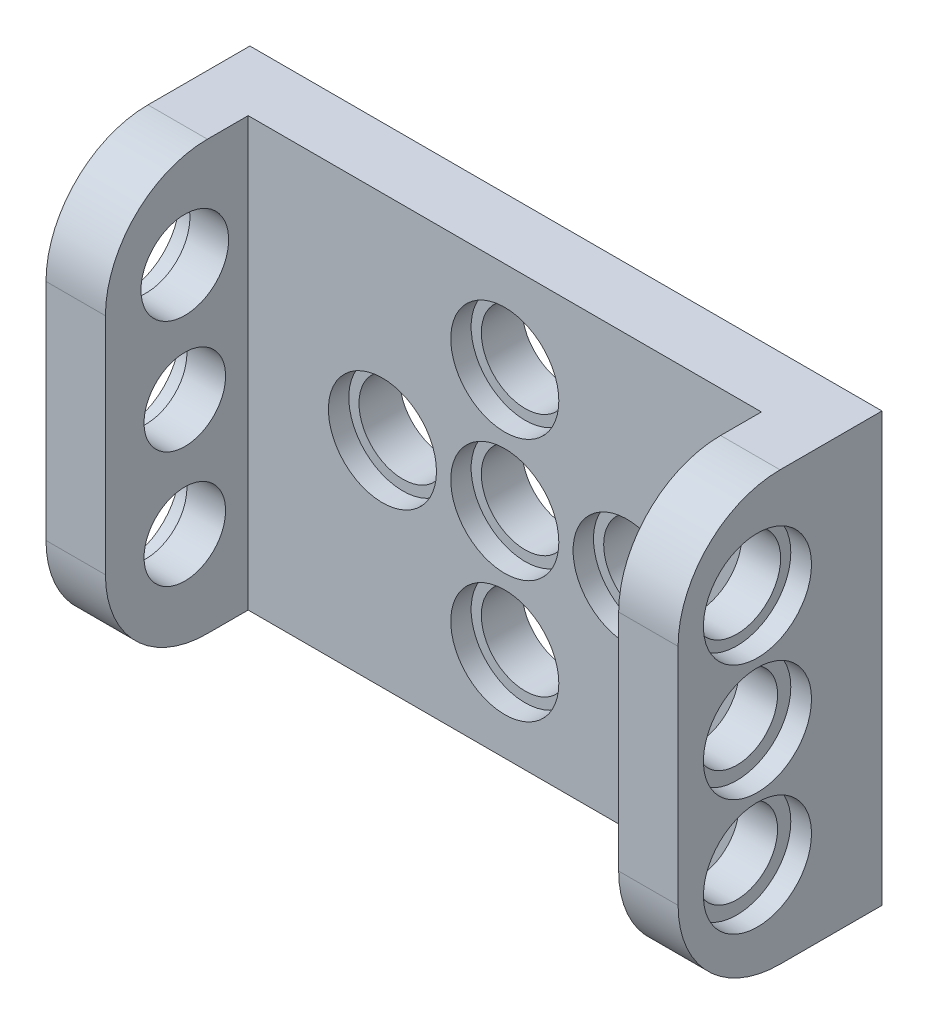
SolidWorks part; units mm, degrees
ref_plane "Alzado" through (0, 0, 0) normal (0, 0, 1) x (1, 0, 0)
ref_plane "Planta" through (0, 0, 0) normal (0, 1, 0) x (1, 0, 0)
ref_plane "Vista lateral" through (0, 0, 0) normal (1, 0, 0) x (0, 0, -1)
sketch "Croquis1" plane through (0, 0, 0) normal (0, 0, 1) x (1, 0, 0)
  line L1 (13.077, 21.3579) -> (44.077, 21.3579)
  line L2 (13.077, 21.3579) -> (13.077, 0.3579)
  line L3 (13.077, 0.3579) -> (44.077, 0.3579)
  line L4 (44.077, 21.3579) -> (44.077, 0.3579)
  dimension "D1" = 21
  dimension "D2" = 31
extrude "Saliente-Extruir1" add sketch "Croquis1" along normal blind 10
sketch "Croquis2" plane through (0, 0, 10) normal (0, 0, 1) x (1, 0, 0)
  line L0 (28.577, 21.3579) -> (28.577, 0.3579) construction
  line L1 (44.077, 21.3579) -> (13.077, 21.3579) construction
  line L2 (13.077, 0.3579) -> (44.077, 0.3579) construction
  line L3 (28.577, 10.8579) -> (44.077, 10.8579) construction
  line L4 (44.077, 0.3579) -> (44.077, 21.3579) construction
  line L6 (15.992, 21.3579) -> (41.162, 21.3579)
  line L7 (15.992, 21.3579) -> (15.992, 0.3579)
  line L8 (15.992, 0.3579) -> (41.162, 0.3579)
  line L9 (41.162, 21.3579) -> (41.162, 0.3579)
  line L10 (15.992, 21.3579) -> (41.162, 0.3579) construction
  line L11 (15.992, 0.3579) -> (41.162, 21.3579) construction
  dimension "D1" = 25.17
extrude "Cortar-Extruir1" cut sketch "Croquis2" against normal blind 7
sketch "Croquis3" plane through (0, 0, 0) normal (0, 0, -1) x (-1, 0, 0)
  line L0 (-28.577, 21.3579) -> (-28.577, 0.3579) construction
  line L1 (-44.077, 21.3579) -> (-13.077, 21.3579) construction
  line L2 (-13.077, 0.3579) -> (-44.077, 0.3579) construction
  line L3 (-28.577, 10.8579) -> (-13.077, 10.8579) construction
  line L4 (-13.077, 21.3579) -> (-13.077, 0.3579) construction
sketch "Croquis4" plane through (0, 0, 0) normal (0, 0, 1) x (1, 0, 0)
  line L0 (28.577, 16.8579) -> (28.577, 10.8579) construction
  line L1 (28.577, 10.8579) -> (28.577, 4.8579) construction
  line L16 (34.577, 10.8579) -> (22.577, 10.8579) construction
  line L18 (22.577, 10.8579) -> (28.577, 16.8579) construction
  line L19 (28.577, 16.8579) -> (34.577, 10.8579) construction
  line L20 (28.577, 4.8579) -> (22.577, 10.8579) construction
  line L21 (34.577, 10.8579) -> (28.577, 4.8579) construction
sketch "Croquis5" plane through (0, 0, 0) normal (0, 0, -1) x (-1, 0, 0)
  circle A0 centre (-28.577, 16.8579) radius 2.15
  circle A1 centre (-22.577, 10.8579) radius 2.15
  circle A2 centre (-34.577, 10.8579) radius 2.15
  circle A3 centre (-28.577, 4.8579) radius 2.15
  circle A4 centre (-28.577, 16.8579) radius 2.65
  circle A5 centre (-22.577, 10.8579) radius 2.65
  circle A6 centre (-34.577, 10.8579) radius 2.65
  circle A7 centre (-28.577, 4.8579) radius 2.65
  circle A8 centre (-28.577, 10.8579) radius 2.15
  circle A9 centre (-28.577, 10.8579) radius 2.65
  dimension "D1" = 5.3
  dimension "D2" = 4.3
extrude "Cortar-Extruir2" cut sketch "Croquis5" against normal through all contours A0 | A8 | A1 | A2 | A3 region at (28.577, 16.8579, 0) region at (22.577, 10.8579, 0) region at (34.577, 10.8579, 0) region at (28.577, 4.8579, 0) region at (28.577, 10.8579, 0)
sketch "Croquis6" plane through (44.077, 0, 0) normal (1, 0, 0) x (0, 0, -1)
  line L0 (-3.0446, 21.3579) -> (-3.0446, 0.3579) construction
  line L1 (-10, 21.3579) -> (0, 21.3579) construction
  line L2 (-10, 0.3579) -> (0, 0.3579) construction
  line L3 (-3.0446, 10.8579) -> (0, 10.8579) construction
  line L4 (0, 21.3579) -> (0, 0.3579) construction
  line L5 (-8.965, 10.8579) -> (-3.2501, 10.8579) construction
  line L6 (-3.2501, 10.8579) -> (2.4649, 10.8579) construction
  line L7 (2.4649, 10.8579) -> (6.3749, 10.8579) construction
  line L8 (-8.965, 10.8579) -> (-12.8751, 10.8579) construction
  line L9 (-8.965, 8.3579) -> (-8.965, 7.8579) construction
  line L10 (-3.2501, 8.3579) -> (-3.2501, 7.8579) construction
  line L11 (2.4649, 8.3579) -> (2.4649, 7.8579) construction
  line L12 (-6.1076, 21.3579) -> (-6.1076, 10.8579) construction
  line L13 (-6.1076, 10.8579) -> (-6.1076, 0.3579) construction
  circle A0 centre (-6.1076, 5.143) radius 2.65
  circle A1 centre (-6.1076, 10.8579) radius 2.65
  circle A2 centre (-6.1076, 16.5729) radius 2.65
  circle A3 centre (-6.1076, 5.143) radius 2
  circle A4 centre (-6.1076, 10.8579) radius 2
  circle A5 centre (-6.1076, 16.5729) radius 2.15
sketch "Croquis7" plane through (44.077, 0, 0) normal (1, 0, 0) x (0, 0, -1)
  line L0 (-6.1076, 10.8579) -> (-6.1076, 0.3579) construction
  line L1 (-10, 0.3579) -> (0, 0.3579) construction
extrude "Cortar-Extruir4" cut sketch "Croquis6" against normal through all contours A5 | A4 | A3 region at (44.077, 5.143, 6.1076) region at (44.077, 10.8579, 6.1076) region at (44.077, 16.5729, 6.1076)
extrude "Cortar-Extruir5" cut sketch "Croquis6<3>" against normal blind 1.015 contours A2 A5 | A1 A4 | A0 A3 region at (44.077, 5.143, 8.6826) region at (44.077, 10.8579, 8.6826) region at (44.077, 16.5729, 8.6826)
sketch "Croquis6<3>" plane through (44.077, 0, 0) normal (1, 0, 0) x (0, 0, -1) same geometry as "Croquis6"
sketch "Croquis9" plane through (13.077, 0, 0) normal (-1, 0, 0) x (0, 0, 1)
  circle A0 centre (6.1076, 16.5729) radius 2.65
  circle A1 centre (6.1076, 10.8579) radius 2.65
  circle A2 centre (6.1076, 5.143) radius 2.65
  circle M1 centre (6.1076, 5.143) radius 2
  circle M2 centre (6.1076, 10.8579) radius 2
  circle M3 centre (6.1076, 16.5729) radius 2.15
extrude "Cortar-Extruir6" cut sketch "Croquis9" against normal blind 1.015 contours A0 M3 | A1 M2 | A2 M1 region at (13.077, 16.5729, 3.5325) region at (13.077, 10.8579, 3.5325) region at (13.077, 5.143, 3.5325)
fillet "Redondeo5" radius 5 4 edges at (14.5345, 0.3579, 10) (42.6195, 0.3579, 10) (42.6195, 21.3579, 10) (14.5345, 21.3579, 10)
sketch "Croquis10" plane through (0, 0, 3) normal (0, 0, 1) x (1, 0, 0)
  circle A0 centre (28.577, 16.8579) radius 2.65
  circle A1 centre (34.577, 10.8579) radius 2.65
  circle A2 centre (28.577, 10.8579) radius 2.65
  circle A3 centre (22.577, 10.8579) radius 2.65
  circle A4 centre (28.577, 4.8579) radius 2.65
  circle M1 centre (28.577, 4.8579) radius 2.15
  circle M2 centre (34.577, 10.8579) radius 2.15
  circle M3 centre (22.577, 10.8579) radius 2.15
  circle M4 centre (28.577, 10.8579) radius 2.15
  circle M5 centre (28.577, 16.8579) radius 2.15
  dimension "D1" = 5.3
extrude "Cortar-Extruir8" cut sketch "Croquis10" against normal blind 1 contours A0 M5 | A1 M2 | A2 M4 | A3 M3 | A4 M1 region at (26.0019, 16.8579, 3) region at (32.0019, 10.8579, 3) region at (26.0019, 10.8579, 3) region at (20.0019, 10.8579, 3) region at (26.0019, 4.8579, 3)
